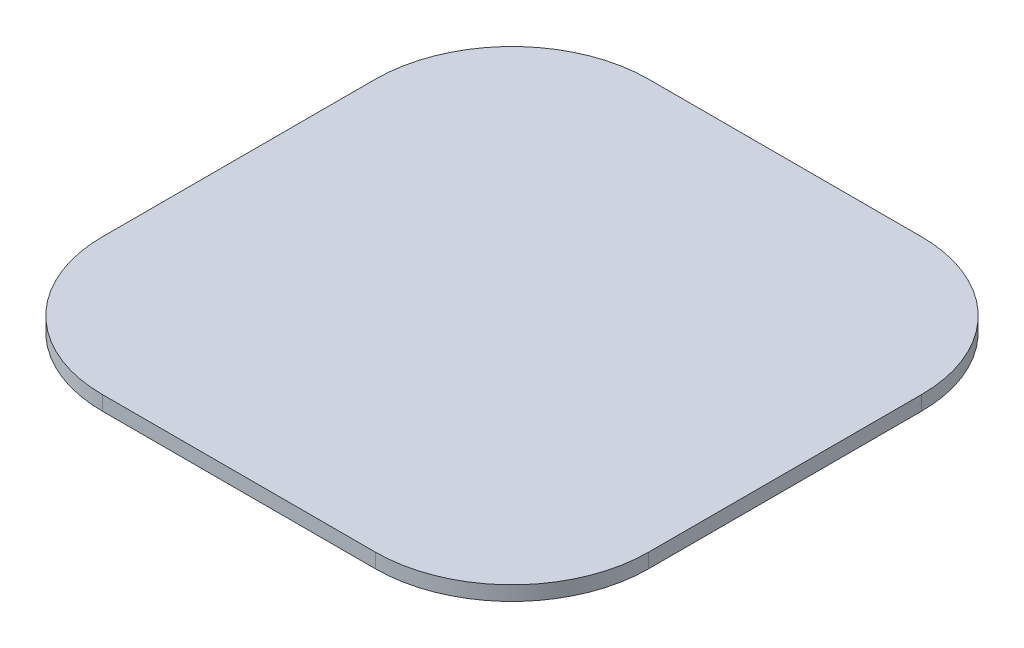
SolidWorks part; units mm, degrees
ref_plane "Front" through (0, 0, 0) normal (0, 0, 1) x (1, 0, 0)
ref_plane "Top" through (0, 0, 0) normal (0, 1, 0) x (1, 0, 0)
ref_plane "Right" through (0, 0, 0) normal (1, 0, 0) x (0, 0, -1)
sketch "Sketch1" plane through (0, 0, 0) normal (0, 1, 0) x (1, 0, 0)
  line L1 (-30, 60) -> (30, 60)
  line L2 (-60, 30) -> (-60, -30)
  line L3 (-30, -60) -> (30, -60)
  line L4 (60, 30) -> (60, -30)
  line L5 (-60, 60) -> (60, -60) construction
  line L6 (-60, -60) -> (60, 60) construction
  arc A0 (30, -60) -> (60, -30) centre (30, -30) ccw
  arc A1 (60, 30) -> (30, 60) centre (30, 30) ccw
  arc A2 (-30, 60) -> (-60, 30) centre (-30, 30) ccw
  arc A3 (-60, -30) -> (-30, -60) centre (-30, -30) ccw
  point P0 (0, 0)
  dimension "D3" = 30
  dimension "D1" = 120
  dimension "D2" = 120
extrude "Boss-Extrude1" add sketch "Sketch1" along normal blind 3.175
